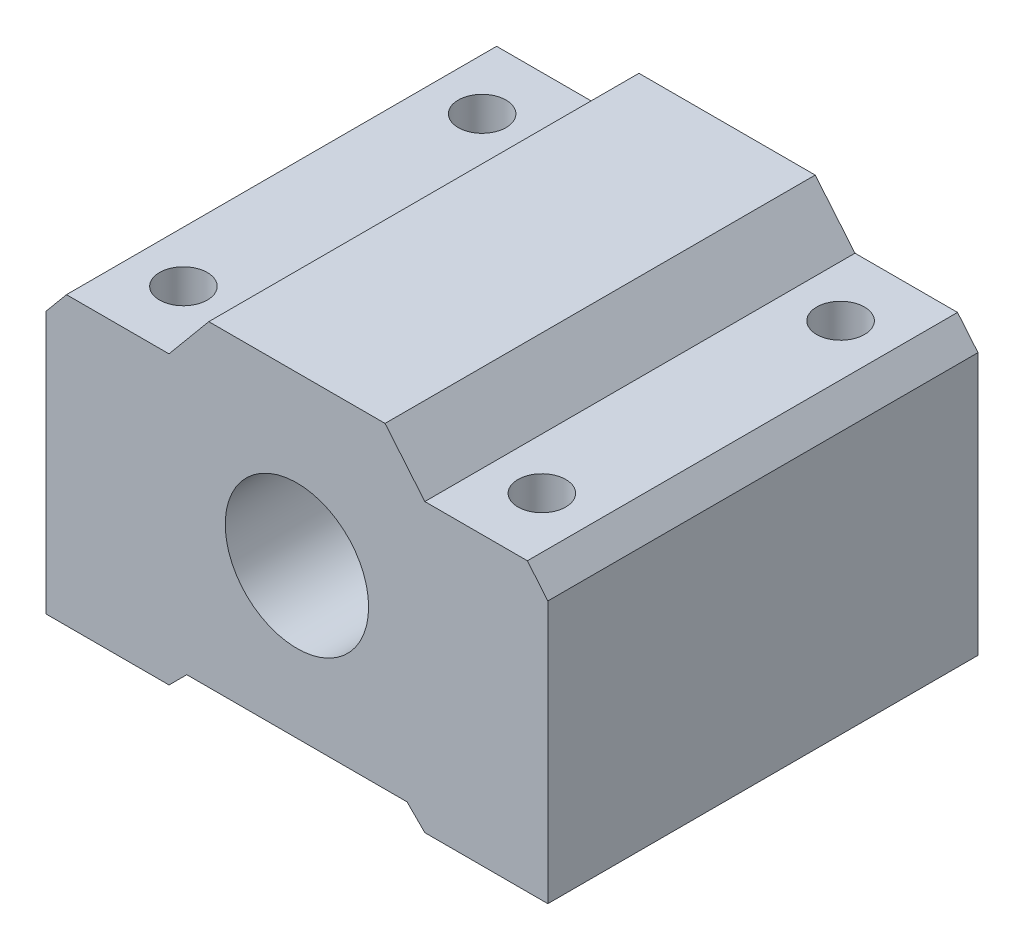
SolidWorks part; units mm, degrees
ref_plane "Front Plane" through (0, 0, 0) normal (0, 0, 1) x (1, 0, 0)
ref_plane "Top Plane" through (0, 0, 0) normal (0, 1, 0) x (1, 0, 0)
ref_plane "Right Plane" through (0, 0, 0) normal (1, 0, 0) x (0, 0, -1)
sketch "Sketch1" plane through (0, 0, 0) normal (0, 0, 1) x (1, 0, 0)
  line L0 (-7.3763, 14) -> (-10.7049, 10)
  line L1 (-21, -14) -> (-12.1932, -14)
  line L2 (-21, -14) -> (-21, 7.9417)
  line L3 (-7.3763, 14) -> (7.3763, 14)
  line L4 (21, -14) -> (21, 7.9417)
  line L5 (12.1932, -14) -> (21, -14)
  line L7 (-10.7049, 10) -> (-19.2872, 10)
  line L8 (-19.2872, 10) -> (-21, 7.9417)
  line L9 (0, 14) -> (0, -14) construction
  line L10 (7.3763, 14) -> (10.7049, 10)
  line L11 (10.7049, 10) -> (19.2872, 10)
  line L12 (19.2872, 10) -> (21, 7.9417)
  line L13 (-12.1932, -14) -> (-10.7049, -14)
  line L14 (-9.2165, -12.5117) -> (9.2165, -12.5117)
  line L15 (-10.7049, -14) -> (-9.2165, -12.5117)
  line L17 (12.1932, -14) -> (10.7049, -14)
  line L18 (10.7049, -14) -> (9.2165, -12.5117)
  circle A0 centre (0, 0) radius 6
  point P0 (0, 0)
  dimension "D3" = 24
  dimension "D1" = 42
  dimension "D2" = 28
  dimension "D4" = 8.5824
  dimension "D5" = 8.5824
  dimension "D6" = 14.7527
  dimension "D7" = 18.4331
extrude "Boss-Extrude1" add sketch "Sketch1" along normal blind 36
sketch "Sketch2" plane through (0, -14, 0) normal (0, -1, 0) x (1, 0, 0)
  line L0 (0, 36) -> (0, 0) construction
  line L1 (-9.2165, 36) -> (9.2165, 36) construction
  line L2 (0, 18) -> (-21, 18) construction
  line L3 (-21, 36) -> (-21, 0) construction
  line L5 (-15, 5.5) -> (15, 5.5) construction
  line L6 (-15, 5.5) -> (-15, 30.5) construction
  line L7 (-15, 30.5) -> (15, 30.5) construction
  line L8 (15, 5.5) -> (15, 30.5) construction
  line L9 (-15, 5.5) -> (15, 30.5) construction
  line L10 (-15, 30.5) -> (15, 5.5) construction
  circle A0 centre (-15, 30.5) radius 2
  circle A1 centre (15, 30.5) radius 2
  circle A2 centre (15, 5.5) radius 2
  circle A3 centre (-15, 5.5) radius 2
  dimension "D1" = 30
  dimension "D2" = 25
extrude "Cut-Extrude1" cut sketch "Sketch2" against normal up to next
